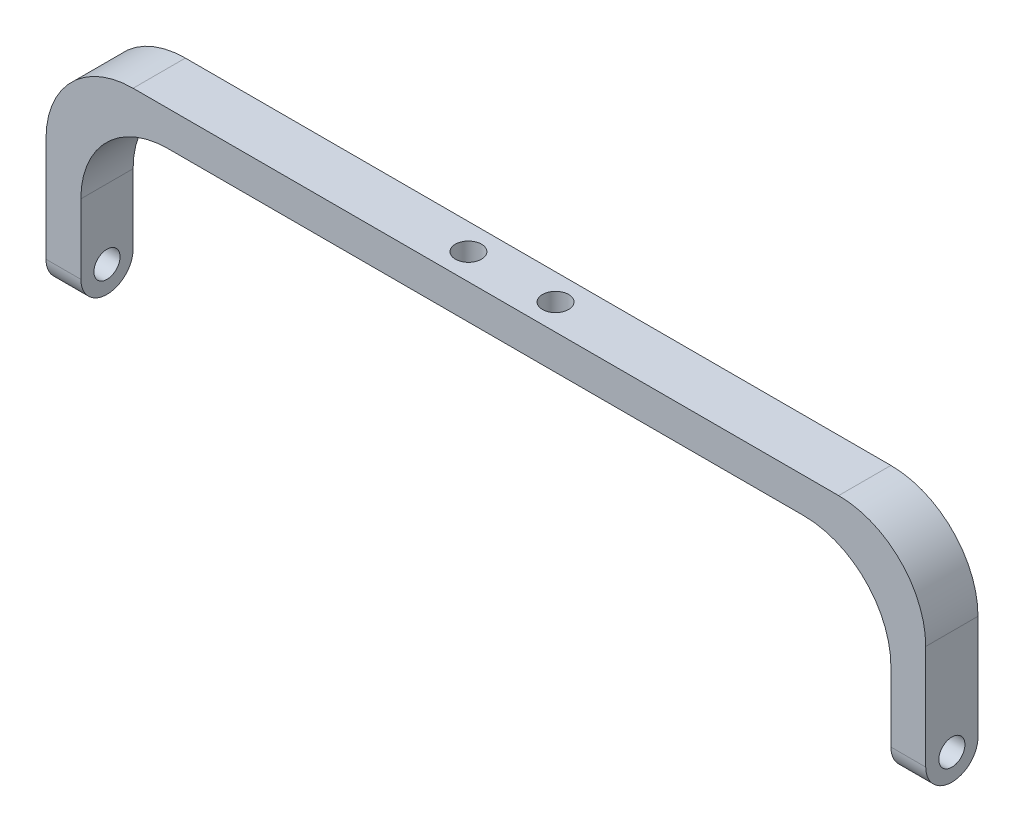
SolidWorks part; units mm, degrees
ref_plane "Front Plane" through (0, 0, 0) normal (0, 0, 1) x (1, 0, 0)
ref_plane "Top Plane" through (0, 0, 0) normal (0, 1, 0) x (1, 0, 0)
ref_plane "Right Plane" through (0, 0, 0) normal (1, 0, 0) x (0, 0, -1)
sketch "Sketch1" plane through (0, 0, 0) normal (0, 0, 1) x (1, 0, 0)
  line L0 (-157.044, 91.3852) -> (-157.044, 116.3852)
  line L1 (-157.044, 116.3852) -> (-56.044, 116.3852)
  line L2 (-56.044, 116.3852) -> (-56.044, 91.3852)
  line L3 (-56.044, 91.3852) -> (-60.044, 91.3852)
  line L4 (-60.044, 91.3852) -> (-60.044, 112.3852)
  line L5 (-60.044, 112.3852) -> (-153.044, 112.3852)
  line L6 (-153.044, 112.3852) -> (-153.044, 91.3852)
  line L7 (-153.044, 91.3852) -> (-157.044, 91.3852)
extrude "Boss-Extrude1" add sketch "Sketch1" along normal blind 6
sketch "Sketch2" plane through (-56.044, 0, 0) normal (1, 0, 0) x (0, 0, -1)
  circle A0 centre (-3, 94.3816) radius 1.5
extrude "Cut-Extrude1" cut sketch "Sketch2" against normal blind 104
fillet "Fillet1" radius 10 4 edges at (-56.044, 116.3852, 3) (-157.044, 116.3852, 3) (-60.044, 112.3852, 3) (-153.044, 112.3852, 3)
fillet "Fillet2" radius 3 4 edges at (-58.044, 91.3852, 6) (-58.044, 91.3852, 0) (-155.044, 91.3852, 0) (-155.044, 91.3852, 6)
sketch "Sketch3" plane through (0, 116.3852, 0) normal (0, 1, 0) x (1, 0, 0)
  circle A0 centre (-101.544, -3) radius 1.5
  circle A1 centre (-111.544, -3) radius 1.5
extrude "Cut-Extrude2" cut sketch "Sketch3" against normal blind 4
